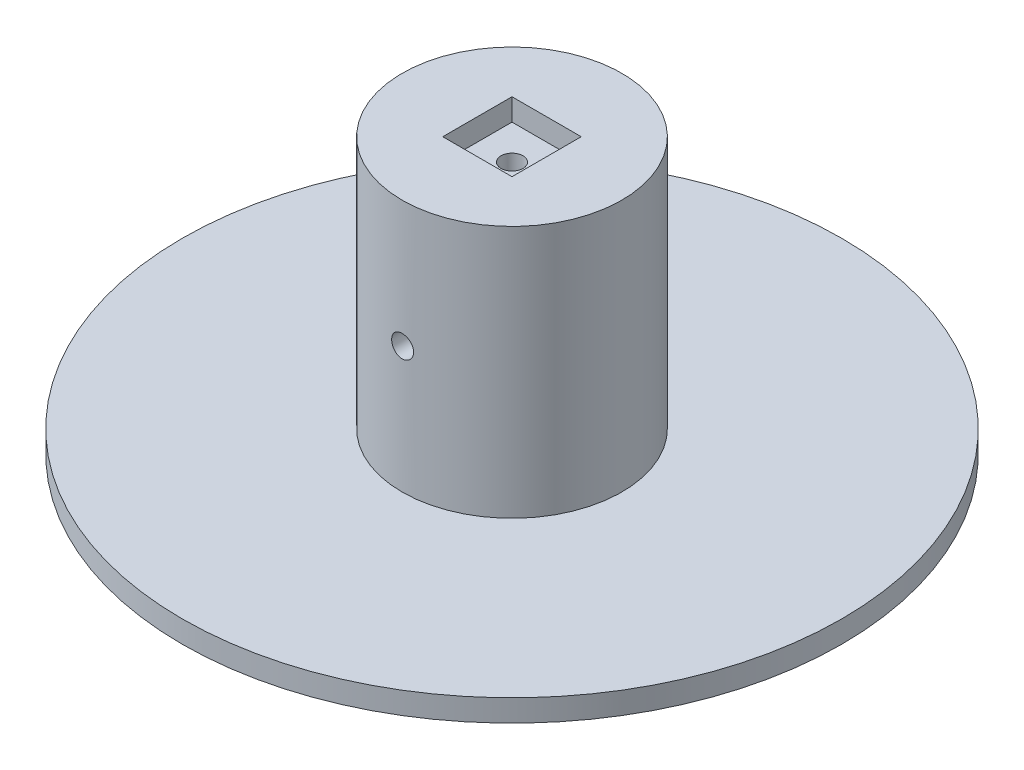
SolidWorks part; units mm, degrees
ref_plane "前视基准面" through (0, 0, 0) normal (0, 0, 1) x (1, 0, 0)
ref_plane "上视基准面" through (0, 0, 0) normal (0, 1, 0) x (1, 0, 0)
ref_plane "右视基准面" through (0, 0, 0) normal (1, 0, 0) x (0, 0, -1)
other "Configuration Table"
sketch "草图1" plane through (0, 0, 0) normal (0, 1, 0) x (1, 0, 0)
  circle A0 centre (0, 0) radius 10
  circle A1 centre (0, 0) radius 30
  circle A2 centre (0, 0) radius 2
  circle A3 centre (0, 0) radius 1
  circle A4 centre (0, 0) radius 1.5
  dimension "D3" = 20
  dimension "D5" = 3
  dimension "D1" = 60
  dimension "D2" = 2
  dimension "D4" = 4
extrude "凸台-拉伸1" add sketch "草图1" along normal blind 2 contours A1
extrude "凸台-拉伸2" add sketch "草图1<8>" along normal blind 25 contours A0
sketch "草图1<8>" plane through (0, 0, 0) normal (0, 1, 0) x (1, 0, 0) same geometry as "草图1"
sketch "草图3" plane through (0, 25, 0) normal (0, 1, 0) x (1, 0, 0)
  line L1 (-3.15, -3.15) -> (3.15, -3.15)
  line L2 (-3.15, -3.15) -> (-3.15, 3.15)
  line L3 (-3.15, 3.15) -> (3.15, 3.15)
  line L4 (3.15, -3.15) -> (3.15, 3.15)
  line L5 (-3.15, -3.15) -> (3.15, 3.15) construction
  line L6 (-3.15, 3.15) -> (3.15, -3.15) construction
  point P0 (0, 0)
  dimension "D1" = 6.3
extrude "切除-拉伸3" cut sketch "草图3" against normal blind 2
extrude "切除-拉伸1" cut sketch "草图1<9>" against normal blind 4 from surface contours A3 starting at face at (0, 25, 0)
sketch "草图1<9>" plane through (0, 0, 0) normal (0, 1, 0) x (1, 0, 0) same geometry as "草图1"
sketch "草图2" plane through (0, 0, 0) normal (0, 0, 1) x (1, 0, 0)
  line L0 (-10, 13.5) -> (10, 13.5) construction
  line L1 (-10, 25) -> (-10, 2) construction
  line L2 (10, 2) -> (10, 25) construction
  circle A0 centre (0, 13.5) radius 1
  point P8 (0, 0)
  dimension "D1" = 2
extrude "切除-拉伸2" cut sketch "草图2" against normal through all both and the other way through all
